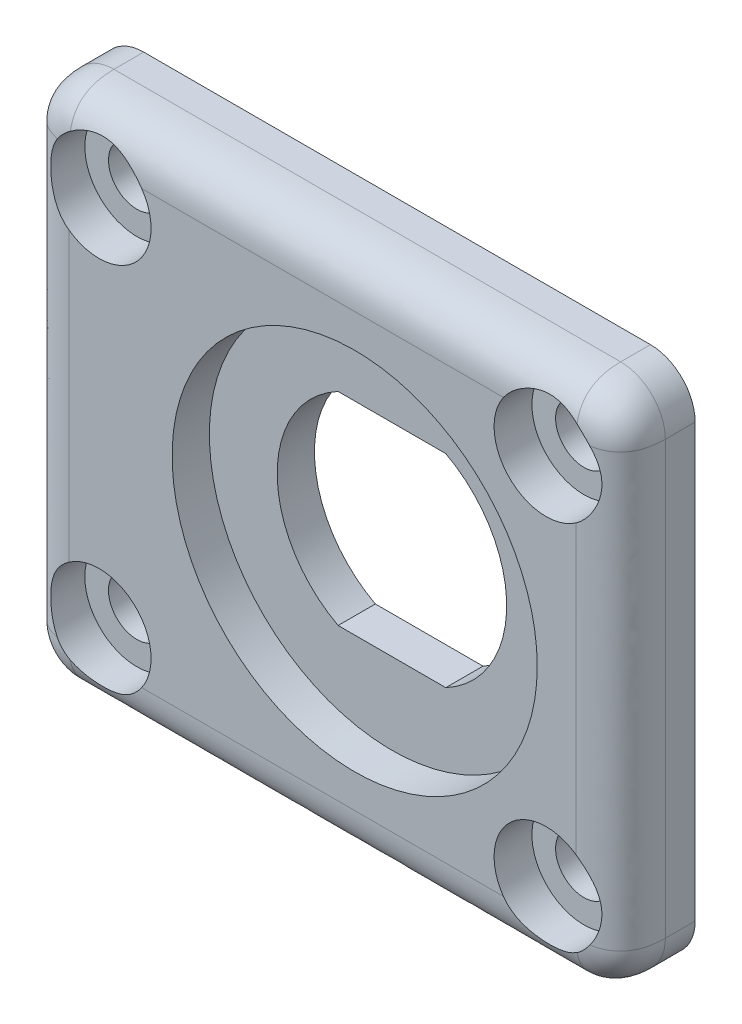
SolidWorks part; units mm, degrees
material "PA Type 6"
ref_plane "Front Plane" through (0, 0, 0) normal (0, 0, 1) x (1, 0, 0)
ref_plane "Top Plane" through (0, 0, 0) normal (0, 1, 0) x (1, 0, 0)
ref_plane "Right Plane" through (0, 0, 0) normal (1, 0, 0) x (0, 0, -1)
sketch "Sketch1" plane through (0, 0, 0) normal (0, 0, 1) x (1, 0, 0)
  line L1 (-20, 17.5) -> (20, 17.5)
  line L2 (-20, 17.5) -> (-20, -17.5)
  line L3 (-20, -17.5) -> (20, -17.5)
  line L4 (20, 17.5) -> (20, -17.5)
  line L5 (-20, 17.5) -> (20, -17.5) construction
  line L6 (-20, -17.5) -> (20, 17.5) construction
  point P0 (0, 0)
  dimension "D1" = 40
  dimension "D2" = 35
extrude "Boss-Extrude1" add sketch "Sketch1" along normal blind 5
sketch "Sketch2" plane through (0, 0, 5) normal (0, 0, 1) x (1, 0, 0)
  line L0 (20, 17.5) -> (-20, 17.5) construction
  line L1 (-20, 17.5) -> (-20, -17.5) construction
  line L2 (0, 17.5) -> (0, -17.5) construction
  line L3 (-20, -17.5) -> (20, -17.5) construction
  line L4 (20, 0) -> (-20, 0) construction
  line L5 (20, -17.5) -> (20, 17.5) construction
  circle A0 centre (-15, 12.5) radius 1.905
  circle A1 centre (15, 12.5) radius 1.905
  circle A2 centre (15, -12.5) radius 1.905
  circle A3 centre (-15, -12.5) radius 1.905
  dimension "D1" = 3.81
  dimension "D2" = 5
  dimension "D3" = 5
extrude "Cut-Extrude1" cut sketch "Sketch2" against normal through all
fillet "Fillet1" radius 3 4 edges at (20, 17.5, 2.5) (20, -17.5, 2.5) (-20, -17.5, 2.5) (-20, 17.5, 2.5)
sketch "Sketch3" plane through (0, 0, 5) normal (0, 0, 1) x (1, 0, 0)
  line L0 (0, 17.5) -> (0, -17.5) construction
  line L1 (17, 17.5) -> (-17, 17.5) construction
  line L2 (-17, -17.5) -> (17, -17.5) construction
  line L3 (-20, 0) -> (20, 0) construction
  line L4 (-20, 14.5) -> (-20, -14.5) construction
  line L5 (20, -14.5) -> (20, 14.5) construction
  circle A0 centre (-15, 12.5) radius 3.4925
  circle A1 centre (15, 12.5) radius 3.4925
  circle A2 centre (15, -12.5) radius 3.4925
  circle A3 centre (-15, -12.5) radius 3.4925
  dimension "D1" = 6.985
extrude "Cut-Extrude2" cut sketch "Sketch3" against normal blind 2.54
fillet "Fillet2" radius 3 4 edges at (20, 0, 5) (0, 17.5, 5) (0, -17.5, 5) (-20, 0, 5) conic rho 0.5
sketch "Sketch5" plane through (0, 0, 0) normal (0, 0, -1) x (-1, 0, 0)
  line L0 (0, 17.5) -> (0, -17.5) construction
  line L1 (-17, 17.5) -> (17, 17.5) construction
  line L2 (17, -17.5) -> (-17, -17.5) construction
  line L3 (-20, 0) -> (20, 0) construction
  line L4 (-20, -14.5) -> (-20, 14.5) construction
  line L5 (20, 14.5) -> (20, -14.5) construction
  line L6 (-9.601, -11) -> (9.601, -11)
  line L7 (13.5, 7.101) -> (13.5, -7.101)
  line L8 (13.5, 0) -> (13.5, -17.5) construction
  line L9 (-9.601, 11) -> (9.601, 11)
  line L10 (-13.5, 7.101) -> (-13.5, -7.101)
  line L11 (-10.5, 12) -> (10.5, 12)
  line L12 (14.5, 8) -> (14.5, -8)
  line L13 (-10.5, -12) -> (10.5, -12)
  line L14 (-14.5, 8) -> (-14.5, -8)
  arc A0 (13.5, -7.101) -> (9.601, -11) centre (14.5, -12) ccw
  arc A1 (13.5, 7.101) -> (9.601, 11) centre (14.5, 12) cw
  arc A2 (-13.5, -7.101) -> (-9.601, -11) centre (-14.5, -12) cw
  arc A3 (-13.5, 7.101) -> (-9.601, 11) centre (-14.5, 12) ccw
  arc A4 (14.5, 8) -> (10.5, 12) centre (14.5, 12) cw
  arc A5 (14.5, -8) -> (10.5, -12) centre (14.5, -12) ccw
  arc A6 (-14.5, -8) -> (-10.5, -12) centre (-14.5, -12) cw
  arc A7 (-14.5, 8) -> (-10.5, 12) centre (-14.5, 12) ccw
  arc A8 (13.5, -7.101) -> (9.601, -11) centre (14.5, -12) ccw construction
  point P24 (0, -11)
  point P29 (0, 11)
  dimension "D3" = 5.5
  dimension "D4" = 5
  dimension "D1" = 6.5
  dimension "D2" = 6.5
extrude "Boss-Extrude2" add sketch "Sketch5" along normal blind 2.5
sketch "Sketch6" plane through (0, 0, 0) normal (0, 0, -1) x (-1, 0, 0)
  line L5 (-13.25, -8) -> (13.25, -8)
  line L10 (13.25, -8) -> (13.25, -6)
  line L11 (-13.25, -6) -> (13.25, -6)
  line L13 (-13.25, -8) -> (-13.25, -6)
  line L14 (17, -17.5) -> (-17, -17.5) construction
  line L15 (0, 17.5) -> (0, -17.5) construction
  line L16 (-17, 17.5) -> (17, 17.5) construction
  point P9 (0, -6)
  dimension "D1" = 2
  dimension "D2" = 9.5
  dimension "D3" = 26.5
extrude "Cut-Extrude4" [suppressed] cut sketch "Sketch6" along normal up to next
sketch "Sketch7" plane through (0, 0, 5) normal (0, 0, 1) x (1, 0, 0)
  line L0 (5.7675, 6.8) -> (-1.4575, 6.8)
  line L1 (2.155, -6.8) -> (2.155, 6.8) construction
  line L2 (-1.4575, -6.8) -> (5.7675, -6.8)
  line L3 (15.8423, 0) -> (-15.8423, 0) construction
  line L4 (12.065, 9.7) -> (-12.065, 9.7) construction
  line L5 (12.065, 9.7) -> (12.065, -9.7) construction
  line L6 (12.065, -9.7) -> (-12.065, -9.7) construction
  line L7 (-12.065, 9.7) -> (-12.065, -9.7) construction
  line L8 (0, 9.7) -> (0, -9.7) construction
  arc A1 (-1.4575, 6.8) -> (-1.4575, -6.8) centre (2.155, 0) ccw
  arc A2 (5.7675, 6.8) -> (5.7675, -6.8) centre (2.155, 0) cw
  point P6 (2.155, 0)
  point P12 (12.065, 0)
  point P15 (0, 0)
  point P18 (0, 0)
  dimension "D2" = 13.6
  dimension "D1" = 7.7
  dimension "D3" = 9.91
  dimension "D4" = 24.13
  dimension "D5" = 19.4
extrude "Cut-Extrude3" cut sketch "Sketch7" against normal up to next
sketch "Sketch8" plane through (0, 0, 0) normal (0, 0, -1) x (-1, 0, 0)
  line L0 (-14.5, -8) -> (14.5, -8)
  line L8 (10.5, -12) -> (-10.5, -12)
  line L9 (10.5, -12) -> (-10.5, -12)
  arc A12 (14.5, -8) -> (10.5, -12) centre (14.5, -12) ccw
  arc A13 (-10.5, -12) -> (-14.5, -8) centre (-14.5, -12) ccw
  arc A14 (14.5, -8) -> (10.5, -12) centre (14.5, -12) ccw
  arc A15 (-10.5, -12) -> (-14.5, -8) centre (-14.5, -12) ccw
  dimension "D1" = 0
extrude "Boss-Extrude4" [suppressed] add sketch "Sketch8" along normal up to surface (2.5 mm away)
sketch "Sketch9" plane through (0, 0, 5) normal (0, 0, 1) x (1, 0, 0)
  circle A0 centre (2.155, 0) radius 12.25
extrude "Cut-Extrude5" cut sketch "Sketch9" against normal offset from surface (2.5 mm away) 2.5 up to face at (2.155, 0, 0)
